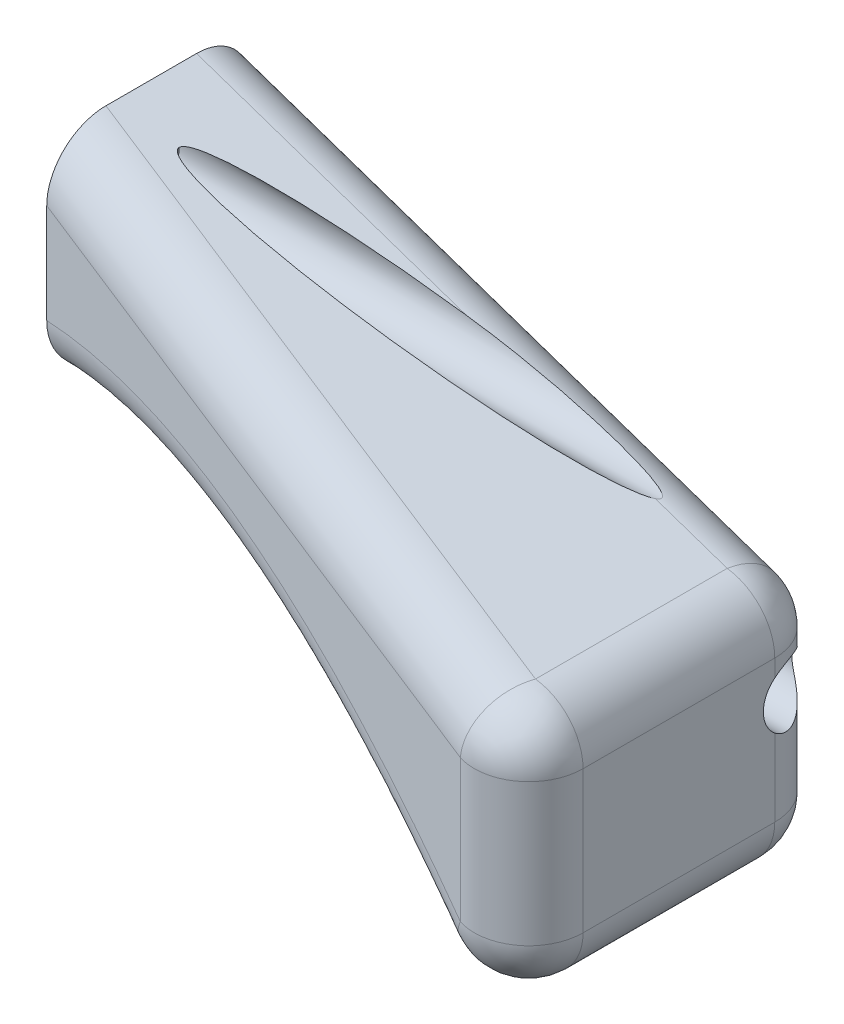
SolidWorks part; units mm, degrees
ref_plane "Front Plane" through (0, 0, 0) normal (0, 0, 1) x (1, 0, 0)
ref_plane "Top Plane" through (0, 0, 0) normal (0, 1, 0) x (1, 0, 0)
ref_plane "Right Plane" through (0, 0, 0) normal (1, 0, 0) x (0, 0, -1)
sketch "Sketch1" plane through (0, 0, 0) normal (1, 0, 0) x (0, 0, -1)
  line L1 (-30, -27.8) -> (30, -27.8)
  line L3 (-30, 27.8) -> (30, 27.8)
  line L4 (30, -27.8) -> (30, 27.8)
  line L5 (-30, -27.8) -> (30, 27.8) construction
  line L6 (-30, 27.8) -> (30, -27.8) construction
  line L7 (-30, 27.8) -> (-62, 27.8)
  line L8 (-30, 27.8) -> (-30, -27.8) construction
  line L9 (-30, -27.8) -> (-62, -27.8)
  line L10 (-62, 27.8) -> (-62, -27.8)
  point P0 (0, 0)
  dimension "D3" = 32
  dimension "D1" = 55.6
  dimension "D2" = 60
extrude "Boss-Extrude1" add sketch "Sketch1" along normal blind 100
sketch "Sketch3" plane through (0, 0, 0) normal (0, 1, 0) x (1, 0, 0)
  line L0 (0, 30) -> (0, 0)
  line L1 (100, 30) -> (0, 30)
  line L2 (100, 30) -> (100, -16)
  line L3 (100, -62) -> (0, -62)
  line L4 (0, -30) -> (0, -62)
  line L5 (0, -30) -> (100, -62)
  line L6 (100, 30) -> (100, -62) construction
  line L7 (0, 30) -> (0, -62) construction
  line L8 (0, 0) -> (100, -16)
  dimension "D1" = 30
  dimension "D2" = 46
  dimension "D3" = 32
  dimension "D4" = 30
extrude "Cut-Extrude3" cut sketch "Sketch3" against normal blind 150 and the other way blind 150
sketch "Sketch4" plane through (0, 0, 0) normal (0, 0, 1) x (1, 0, 0)
  line L1 (100, 15.21) -> (0, 27.8)
  line L4 (100, 15.21) -> (100, 27.8)
  line L5 (100, 27.8) -> (0, 27.8)
  line L6 (0, -4.3695) -> (0, -27.8)
  line L7 (100, 27.8) -> (0, 27.8)
  line L12 (100, -27.8) -> (100, 27.8)
  line L13 (0, -27.8) -> (100, -27.8)
  line L14 (0, 27.8) -> (0, -27.8)
  line L15 (100, 27.8) -> (0, 27.8) construction
  line L16 (100, -27.8) -> (100, 27.8) construction
  line L17 (0, -27.8) -> (100, -27.8) construction
  line L18 (0, 27.8) -> (0, -27.8) construction
  line L19 (0, -27.8) -> (100, -27.8)
  line L25 (0, 27.8) -> (0, -27.8) construction
  spline S0 degree 2 poles (100, -27.8) (45.8867, 11.487) (0, -4.3695) knots 0 0 0 0.734969 0.734969 0.734969
  point P0 (100, 15.21)
  point P5 (0, 0)
  point P9 (32.7628, 0)
  point P18 (32.7628, 0)
  dimension "D2" = 12.59
  dimension "D4" = 23.4305
  dimension "D5" = 27.8
  dimension "D6" = 32.7628
  dimension "D1" = 0
extrude "Cut-Extrude6" cut sketch "Sketch4" against normal blind 150 and the other way blind 150
fillet "Fillet7" radius 8 8 edges at (100, -6.295, 62) (100, -6.295, 16) (100, -27.8, 39) (100, 15.21, 39) (50, 21.505, 8) (50, 21.505, 46) (54.8806, -4.1776, 8.7809) (24.1052, 0.1377, 37.7137)
sketch "Sketch5" plane through (0, 0, 0) normal (-1, 0, 0) x (0, 0, 1)
  line L0 (20, 12.104) -> (30, 12.104) construction
  line L5 (20, 22.104) -> (20, 2.104) construction
  line L8 (20, 12.104) -> (20, 30.9633) construction
  line L9 (20, 2.104) -> (29.4718, 2.104) construction
  line L10 (20, 2.104) -> (20, -6.9397) construction
  line L12 (30, 4.7781) -> (30, 19.4299) construction
  circle A0 centre (20, 22.104) radius 2.3
  circle A1 centre (20, 2.104) radius 2.3
  point P0 (20, 12.104)
  point P1 (30, 12.104)
  point P2 (0, 0)
  point P11 (20, 12.104)
  dimension "D3" = 4.6
  dimension "D1" = 20
  dimension "D2" = 10
  dimension "D6" = 10
extrude "Cut-Extrude7" cut sketch "Sketch5" against normal blind 5
sketch "Sketch6" plane through (5, 0, 0) normal (-1, 0, 0) x (0, 0, 1)
  circle A0 centre (20, 22.104) radius 4.5
  circle A1 centre (20, 2.104) radius 4.5
  dimension "D1" = 9
extrude "Cut-Extrude8" cut sketch "Sketch6" against normal blind 150
